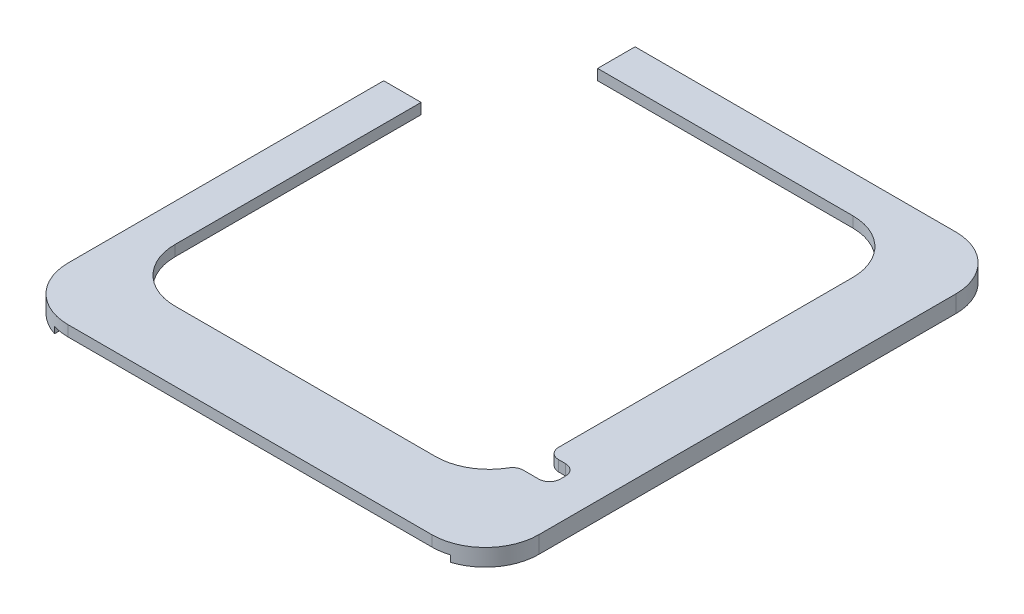
SolidWorks part; units mm, degrees
ref_plane "前视基准面" through (0, 0, 0) normal (0, 0, 1) x (1, 0, 0)
ref_plane "上视基准面" through (0, 0, 0) normal (0, 1, 0) x (1, 0, 0)
ref_plane "右视基准面" through (0, 0, 0) normal (1, 0, 0) x (0, 0, -1)
other "Configuration Table"
sketch "草图2" plane through (0, 0, 0) normal (0, 1, 0) x (1, 0, 0)
  line L0 (0, 0) -> (0, 57) construction
  line L1 (0, 57) -> (19, 57) construction
  line L2 (19, 57) -> (19, 87) construction
  line L4 (84.7, 70) -> (84.7, 0) construction
  line L5 (0, 0) -> (84.7, 0) construction
  line L6 (74.7, 87) -> (74.7, 70) construction
  line L7 (74.7, 70) -> (84.7, 70) construction
  line L8 (42.35, 0) -> (42.35, 105.3239) construction
  line L9 (0, 68) -> (7, 68)
  line L10 (13, 87) -> (18, 87)
  line L12 (0, -20) -> (63.3763, -20) construction
  line L13 (88, 87) -> (88, 71)
  line L14 (7, 68) -> (7, 58)
  line L15 (7, 58) -> (0, 58)
  line L16 (0, -1) -> (7, -1)
  line L17 (7, -1) -> (7, -11)
  line L18 (0, 68) -> (0, 58)
  line L19 (0, -1) -> (0, -11)
  line L20 (18, 87) -> (18, 80)
  line L21 (18, 80) -> (13, 80)
  line L22 (13, 80) -> (13, 87)
  line L23 (75.7, 87) -> (75.7, 71)
  line L24 (75.7, 71) -> (88, 71)
  line L25 (75.7, 87) -> (88, 87)
  line L26 (19, 87) -> (74.7, 87) construction
  line L27 (88, -1) -> (81, -1)
  line L28 (81, -1) -> (81, -11)
  line L29 (63.3763, -20) -> (88, -20) construction
  line L30 (88, -1) -> (88, -11)
  line L31 (0, -11) -> (7, -11)
  line L32 (81, -11) -> (88, -11)
  point P22 (47.928, -20)
  point P35 (80.3877, -20)
  point P36 (63.3763, -20)
  point P37 (88, 79)
  point P38 (0, 0)
  dimension "D1" = 57
  dimension "D2" = 19
  dimension "D3" = 30
  dimension "D4" = 55.7
  dimension "D5" = 10
  dimension "D6" = 70
  dimension "D7" = 88
  dimension "D8" = 1
  dimension "D9" = 1
  dimension "D10" = 7
  dimension "D11" = 10
  dimension "D12" = 7
  dimension "D13" = 1
  dimension "D14" = 107
  dimension "D15" = 1
  dimension "D16" = 5
  dimension "D17" = 7
  dimension "D18" = 1
  dimension "D19" = 7
  dimension "D20" = 10
extrude "凸台-拉伸1" add sketch "草图2" along normal blind 1.2
sketch "草图3" plane through (0, 1.2, 0) normal (0, 1, 0) x (1, 0, 0)
  line L0 (0, -1) -> (0, -11) construction
  line L2 (75.7, 71) -> (75.7, 2)
  line L4 (88, -11) -> (88, -1) construction
  line L6 (7, 2) -> (75.7, 2)
  line L8 (88, 87) -> (75.7, 87) construction
  line L9 (75.7, 87) -> (75.7, 71) construction
  line L11 (88, 71) -> (88, 87) construction
  line L13 (18, 87) -> (13, 87) construction
  line L14 (13, 87) -> (13, 80) construction
  line L15 (13, 80) -> (18, 80) construction
  line L16 (0, 68) -> (0, 58) construction
  line L17 (7, -1) -> (0, -1) construction
  line L18 (7, 58) -> (7, 68) construction
  line L19 (7, 68) -> (0, 68) construction
  line L20 (0, -1) -> (0, -11)
  line L21 (0, -11) -> (11.4018, -11)
  line L24 (88, -11) -> (88, -1)
  line L27 (76.7889, -11) -> (88, -11)
  line L28 (88, 87) -> (75.7, 87)
  line L29 (75.7, 80) -> (75.7, 71)
  line L31 (88, 71) -> (88, 87)
  line L33 (18, 87) -> (13, 87)
  line L34 (13, 87) -> (13, 80)
  line L35 (13, 80) -> (18, 80)
  line L36 (0, 68) -> (0, 58)
  line L38 (7, 58) -> (7, 68)
  line L39 (7, 68) -> (0, 68)
  line L41 (11.4018, -11) -> (76.7889, -11)
  line L42 (0, 58) -> (0, -1)
  line L43 (88, 71) -> (88, -1)
  line L44 (18, 87) -> (75.7, 87)
  line L45 (18, 80) -> (75.7, 80)
  line L46 (7, 58) -> (7, 2)
  line L47 (0, -11) -> (7, -11) construction
  line L48 (81, -11) -> (88, -11) construction
  point P12 (75.7, -11)
  dimension "D1" = 3
extrude "凸台-拉伸2" add sketch "草图3" along normal blind 2
sketch "草图4" plane through (0, 0, 0) normal (0, -1, 0) x (1, 0, 0)
  line L0 (0, -68) -> (0, -58) construction
  line L1 (0, -58) -> (18, -58)
  line L2 (0, -58) -> (0, -87)
  line L3 (0, -87) -> (18, -87)
  line L4 (18, -58) -> (18, -87)
  line L5 (18, -87) -> (13, -87) construction
  line L6 (0, -58) -> (7, -58) construction
  point P8 (0, -58)
  point P9 (18, -87)
extrude "切除-拉伸1" cut sketch "草图4" against normal through all
fillet "圆角1" radius 10 3 edges at (75.7, 2.2, -80) (7, 2.2, -2) (75.7, 2.2, -2)
fillet "圆角2" radius 10 3 edges at (88, 1.6, -87) (0, 1.6, 11) (88, 1.6, 11)
sketch "草图5" plane through (0, 3.2, 0) normal (0, 1, 0) x (1, 0, 0)
  line L0 (88, 10.5) -> (60.4406, 10.5) construction
  line L1 (88, -1) -> (88, 77) construction
  line L2 (78, 87) -> (18, 87) construction
  line L3 (0, 58) -> (0, -1) construction
  line L4 (74.8652, 8) -> (81, 8)
  line L5 (74.8652, 8) -> (74.8652, 13)
  line L6 (74.8652, 13) -> (81, 13)
  line L7 (81, 8) -> (81, 13)
  arc A0 (65.7, 2) -> (75.7, 12) centre (65.7, 12) ccw construction
  point P12 (74.8102, 7.8763)
  dimension "D1" = 76.5
  dimension "D2" = 5
  dimension "D3" = 81
extrude "切除-拉伸2" cut sketch "草图5" against normal through all
fillet "圆角3" radius 2 4 edges at (81, 2.2, -8) (81, 2.2, -13) (74.8652, 2.2, -8) (75.7, 2.2, -13)
sketch "草图6" plane through (0, 1.2, 0) normal (0, -1, 0) x (1, 0, 0)
  line L0 (75.7, -71) -> (88, -71) construction
  line L1 (88, 1) -> (85.3, 1)
  line L2 (88, 1) -> (88, -71)
  line L3 (88, -71) -> (85.3, -71)
  line L4 (85.3, 1) -> (85.3, -71)
  dimension "D1" = 2.7
extrude "凸台-拉伸3" add sketch "草图6" along normal up to surface (1.2 mm away) up to face at (83.8541, 0, 4.5619)
sketch "草图7" plane through (0, 1.2, 0) normal (0, 1, 0) x (1, 0, 0)
  line L0 (17, -6) -> (65.7, -6) construction
  line L1 (10, -11) -> (78, -11) construction
  text T0 "<b>Polaroid Fixer</b>" font "Roboto Mono" height 4
  point P5 (0, 0)
  dimension "D1" = 5
extrude "切除-拉伸5" cut sketch "草图7" along normal blind 0.6
